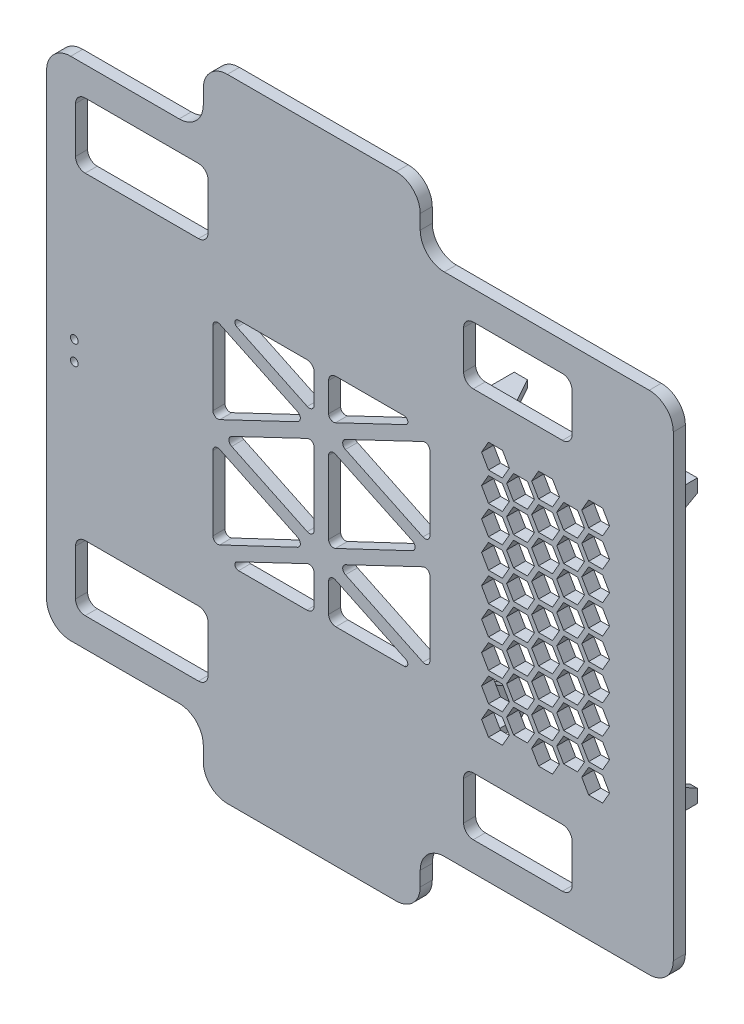
SolidWorks part; units mm, degrees
ref_plane "前视基准面" through (0, 0, 0) normal (0, 0, 1) x (1, 0, 0)
ref_plane "上视基准面" through (0, 0, 0) normal (0, 1, 0) x (1, 0, 0)
ref_plane "右视基准面" through (0, 0, 0) normal (1, 0, 0) x (0, 0, -1)
sketch "草图1" plane through (0, 0, 0) normal (0, 0, 1) x (1, 0, 0)
  line L2 (-130, 95) -> (-130, -95)
  line L3 (-120, -105) -> (-75, -105)
  line L4 (130, 95) -> (130, -95)
  line L5 (126.7518, 102.3765) -> (130, 105) construction
  line L6 (-130, -105) -> (-126.7518, -102.3765) construction
  line L9 (-65, -115) -> (-65, -121)
  line L10 (-55, -131) -> (15, -131)
  line L11 (25, -121) -> (25, -115)
  line L13 (35, -105) -> (120, -105)
  line L14 (126.7518, -102.3765) -> (130, -105) construction
  line L15 (-130, 105) -> (-126.7518, 102.3765) construction
  line L16 (-130, 0) -> (130, 0) construction
  line L17 (35, 105) -> (120, 105)
  line L18 (25, 121) -> (25, 115)
  line L19 (-55, 131) -> (15, 131)
  line L20 (-65, 115) -> (-65, 121)
  line L21 (-120, 105) -> (-75, 105)
  arc A1 (-120, -105) -> (-130, -95) centre (-120, -95) cw
  arc A3 (120, -105) -> (130, -95) centre (120, -95) ccw
  arc A8 (-65, -115) -> (-75, -105) centre (-75, -115) ccw
  arc A9 (25, -115) -> (35, -105) centre (35, -115) cw
  arc A10 (-55, -131) -> (-65, -121) centre (-55, -121) cw
  arc A11 (15, -131) -> (25, -121) centre (15, -121) ccw
  arc A12 (15, 131) -> (25, 121) centre (15, 121) cw
  arc A13 (-55, 131) -> (-65, 121) centre (-55, 121) ccw
  arc A14 (25, 115) -> (35, 105) centre (35, 115) ccw
  arc A15 (-65, 115) -> (-75, 105) centre (-75, 115) cw
  arc A16 (120, 105) -> (130, 95) centre (120, 95) cw
  arc A17 (-120, 105) -> (-130, 95) centre (-120, 95) ccw
  point P0 (0, 0)
  point P40 (25, -105)
  point P45 (25, 105)
  dimension "D2" = 10
  dimension "D3" = 65
  dimension "D4" = 10
  dimension "D5" = 105
  dimension "D7" = 10
  dimension "D8" = 10
  dimension "D10" = 10
  dimension "D12" = 10
  dimension "D13" = 105
  dimension "D18" = 90
  dimension "D19" = 6
extrude "凸台-拉伸1" add sketch "草图1" along normal blind 5
sketch "草图4" plane through (0, 0, 0) normal (0, 0, -1) x (-1, 0, 0)
  line L0 (-39, -47.5) -> (-39, -58.5)
  line L1 (-39, -58.5) -> (-50, -58.5)
  line L2 (-50, -58.5) -> (-50, -55.5)
  line L3 (-50, -55.5) -> (-42, -55.5)
  line L4 (-42, -55.5) -> (-42, -47.5)
  line L5 (-42, -47.5) -> (-39, -47.5)
  line L6 (-130, 0) -> (-25.5592, 0) construction
  line L7 (-130, -95) -> (-130, 95) construction
  line L10 (-130, -95) -> (-130, 95) construction
  dimension "D1" = 11
  dimension "D2" = 11
  dimension "D3" = 3
  dimension "D4" = 3
  dimension "D5" = 80
  dimension "D7" = 55.5
extrude "凸台-拉伸2" add sketch "草图4" along normal blind 20
sketch "草图5" plane through (0, -58.5, 0) normal (0, -1, 0) x (1, 0, 0)
  line L0 (50, -10) -> (44.5, -20)
  line L1 (50, -20) -> (50, 0) construction
  line L2 (50, -20) -> (39, -20) construction
  line L3 (44.5, -20) -> (50, -20)
  line L4 (50, -20) -> (50, -10)
  dimension "D1" = 10
  dimension "D2" = 5.5
extrude "切除-拉伸3" cut sketch "草图5" against normal blind 10
sketch "草图6" plane through (39, 0, 0) normal (-1, 0, 0) x (0, 0, 1)
  line L0 (-20, -53) -> (-10, -47.5)
  line L1 (-20, -58.5) -> (-20, -47.5) construction
  line L2 (-20, -47.5) -> (0, -47.5) construction
  line L3 (-10, -47.5) -> (-20, -47.5)
  line L4 (-20, -47.5) -> (-20, -53)
  dimension "D1" = 10
  dimension "D2" = 5.5
extrude "切除-拉伸4" cut sketch "草图6" against normal blind 10
ref_plane "基准面2" through (77, 0, 0) normal (1, 0, 0) x (0, 0, -1)
mirror "镜向1" about plane through (77, 0, 0) normal (1, 0, 0) of "凸台-拉伸2", "切除-拉伸4", "切除-拉伸3"
mirror "镜向2" about plane through (0, 0, 0) normal (0, 1, 0) of "镜向1"
sketch "草图7" plane through (0, 0, 0) normal (0, 0, -1) x (-1, 0, 0)
  line L4 (-112, -55.5) -> (-104, -55.5) construction
  line L5 (-112, 47.5) -> (-112, 55.5) construction
  line L6 (-112, 55.5) -> (-104, 55.5) construction
  line L7 (-92.013, 36) -> (-94.8997, 41)
  line L8 (-94.8997, 41) -> (-100.6732, 41)
  line L9 (-100.6732, 41) -> (-103.56, 36)
  line L10 (-103.56, 36) -> (-100.6732, 31)
  line L11 (-100.6732, 31) -> (-94.8997, 31)
  line L12 (-94.8997, 31) -> (-92.013, 36)
  line L13 (-77.0019, 36) -> (-97.7865, 36) construction
  line L14 (-74.1151, 31) -> (-71.2284, 36)
  line L15 (-71.2284, 36) -> (-74.1151, 41)
  line L16 (-74.1151, 41) -> (-79.8886, 41)
  line L17 (-79.8886, 41) -> (-82.7754, 36)
  line L18 (-82.7754, 36) -> (-79.8886, 31)
  line L19 (-79.8886, 31) -> (-74.1151, 31)
  line L20 (-92.013, 24) -> (-94.8997, 29)
  line L21 (-93.1677, 30) -> (-90.2809, 25)
  line L22 (-90.2809, 25) -> (-84.5074, 25)
  line L23 (-84.5074, 25) -> (-81.6207, 30)
  line L24 (-81.6207, 30) -> (-84.5074, 35)
  line L25 (-84.5074, 35) -> (-90.2809, 35)
  line L26 (-90.2809, 35) -> (-93.1677, 30)
  line L27 (-84.5074, 37) -> (-81.6207, 42)
  line L28 (-81.6207, 42) -> (-84.5074, 47)
  line L29 (-84.5074, 47) -> (-90.2809, 47)
  line L30 (-90.2809, 47) -> (-93.1677, 42)
  line L31 (-93.1677, 42) -> (-90.2809, 37)
  line L32 (-90.2809, 37) -> (-84.5074, 37)
  line L33 (-79.8886, 43) -> (-74.1151, 43)
  line L34 (-74.1151, 43) -> (-71.2284, 48)
  line L35 (-71.2284, 48) -> (-74.1151, 53)
  line L36 (-74.1151, 53) -> (-79.8886, 53)
  line L37 (-79.8886, 53) -> (-82.7754, 48)
  line L38 (-82.7754, 48) -> (-79.8886, 43)
  line L39 (-94.8997, 43) -> (-92.013, 48)
  line L40 (-92.013, 48) -> (-94.8997, 53)
  line L41 (-94.8997, 53) -> (-100.6732, 53)
  line L42 (-100.6732, 53) -> (-103.56, 48)
  line L43 (-103.56, 48) -> (-100.6732, 43)
  line L44 (-100.6732, 43) -> (-94.8997, 43)
  line L45 (-72.3831, 42) -> (-69.4963, 37)
  line L46 (-69.4963, 37) -> (-63.7228, 37)
  line L47 (-63.7228, 37) -> (-60.8361, 42)
  line L48 (-60.8361, 42) -> (-63.7228, 47)
  line L49 (-63.7228, 47) -> (-69.4963, 47)
  line L50 (-69.4963, 47) -> (-72.3831, 42)
  line L51 (-94.8997, 29) -> (-100.6732, 29)
  line L52 (-100.6732, 29) -> (-103.56, 24)
  line L53 (-103.56, 24) -> (-100.6732, 19)
  line L54 (-100.6732, 19) -> (-94.8997, 19)
  line L55 (-94.8997, 19) -> (-92.013, 24)
  line L56 (-93.1677, 18) -> (-90.2809, 13)
  line L57 (-90.2809, 13) -> (-84.5074, 13)
  line L58 (-84.5074, 13) -> (-81.6207, 18)
  line L59 (-81.6207, 18) -> (-84.5074, 23)
  line L60 (-84.5074, 23) -> (-90.2809, 23)
  line L61 (-90.2809, 23) -> (-93.1677, 18)
  line L62 (-74.1151, 19) -> (-71.2284, 24)
  line L63 (-71.2284, 24) -> (-74.1151, 29)
  line L64 (-74.1151, 29) -> (-79.8886, 29)
  line L65 (-79.8886, 29) -> (-82.7754, 24)
  line L66 (-82.7754, 24) -> (-79.8886, 19)
  line L67 (-79.8886, 19) -> (-74.1151, 19)
  line L68 (-72.3831, 30) -> (-69.4963, 25)
  line L69 (-69.4963, 25) -> (-63.7228, 25)
  line L70 (-63.7228, 25) -> (-60.8361, 30)
  line L71 (-60.8361, 30) -> (-63.7228, 35)
  line L72 (-63.7228, 35) -> (-69.4963, 35)
  line L73 (-69.4963, 35) -> (-72.3831, 30)
  line L74 (-92.013, 12) -> (-94.8997, 17)
  line L75 (-94.8997, 17) -> (-100.6732, 17)
  line L76 (-100.6732, 17) -> (-103.56, 12)
  line L77 (-103.56, 12) -> (-100.6732, 7)
  line L78 (-100.6732, 7) -> (-94.8997, 7)
  line L79 (-94.8997, 7) -> (-92.013, 12)
  line L80 (-93.1677, 6) -> (-90.2809, 1)
  line L81 (-90.2809, 1) -> (-84.5074, 1)
  line L82 (-84.5074, 1) -> (-81.6207, 6)
  line L83 (-81.6207, 6) -> (-84.5074, 11)
  line L84 (-84.5074, 11) -> (-90.2809, 11)
  line L85 (-90.2809, 11) -> (-93.1677, 6)
  line L86 (-74.1151, 7) -> (-71.2284, 12)
  line L87 (-71.2284, 12) -> (-74.1151, 17)
  line L88 (-74.1151, 17) -> (-79.8886, 17)
  line L89 (-79.8886, 17) -> (-82.7754, 12)
  line L90 (-82.7754, 12) -> (-79.8886, 7)
  line L91 (-79.8886, 7) -> (-74.1151, 7)
  line L92 (-72.3831, 18) -> (-69.4963, 13)
  line L93 (-69.4963, 13) -> (-63.7228, 13)
  line L94 (-63.7228, 13) -> (-60.8361, 18)
  line L95 (-60.8361, 18) -> (-63.7228, 23)
  line L96 (-63.7228, 23) -> (-69.4963, 23)
  line L97 (-69.4963, 23) -> (-72.3831, 18)
  line L98 (-92.013, 0) -> (-94.8997, 5)
  line L99 (-94.8997, 5) -> (-100.6732, 5)
  line L100 (-100.6732, 5) -> (-103.56, 0)
  line L101 (-103.56, 0) -> (-100.6732, -5)
  line L102 (-100.6732, -5) -> (-94.8997, -5)
  line L103 (-94.8997, -5) -> (-92.013, 0)
  line L104 (-93.1677, -6) -> (-90.2809, -11)
  line L105 (-90.2809, -11) -> (-84.5074, -11)
  line L106 (-84.5074, -11) -> (-81.6207, -6)
  line L107 (-81.6207, -6) -> (-84.5074, -1)
  line L108 (-84.5074, -1) -> (-90.2809, -1)
  line L109 (-90.2809, -1) -> (-93.1677, -6)
  line L110 (-74.1151, -5) -> (-71.2284, 0)
  line L111 (-71.2284, 0) -> (-74.1151, 5)
  line L112 (-74.1151, 5) -> (-79.8886, 5)
  line L113 (-79.8886, 5) -> (-82.7754, 0)
  line L114 (-82.7754, 0) -> (-79.8886, -5)
  line L115 (-79.8886, -5) -> (-74.1151, -5)
  line L116 (-72.3831, 6) -> (-69.4963, 1)
  line L117 (-69.4963, 1) -> (-63.7228, 1)
  line L118 (-63.7228, 1) -> (-60.8361, 6)
  line L119 (-60.8361, 6) -> (-63.7228, 11)
  line L120 (-63.7228, 11) -> (-69.4963, 11)
  line L121 (-69.4963, 11) -> (-72.3831, 6)
  line L122 (-92.013, -12) -> (-94.8997, -7)
  line L123 (-94.8997, -7) -> (-100.6732, -7)
  line L124 (-100.6732, -7) -> (-103.56, -12)
  line L125 (-103.56, -12) -> (-100.6732, -17)
  line L126 (-100.6732, -17) -> (-94.8997, -17)
  line L127 (-94.8997, -17) -> (-92.013, -12)
  line L128 (-93.1677, -18) -> (-90.2809, -23)
  line L129 (-90.2809, -23) -> (-84.5074, -23)
  line L130 (-84.5074, -23) -> (-81.6207, -18)
  line L131 (-81.6207, -18) -> (-84.5074, -13)
  line L132 (-84.5074, -13) -> (-90.2809, -13)
  line L133 (-90.2809, -13) -> (-93.1677, -18)
  line L134 (-74.1151, -17) -> (-71.2284, -12)
  line L135 (-71.2284, -12) -> (-74.1151, -7)
  line L136 (-74.1151, -7) -> (-79.8886, -7)
  line L137 (-79.8886, -7) -> (-82.7754, -12)
  line L138 (-82.7754, -12) -> (-79.8886, -17)
  line L139 (-79.8886, -17) -> (-74.1151, -17)
  line L140 (-72.3831, -6) -> (-69.4963, -11)
  line L141 (-69.4963, -11) -> (-63.7228, -11)
  line L142 (-63.7228, -11) -> (-60.8361, -6)
  line L143 (-60.8361, -6) -> (-63.7228, -1)
  line L144 (-63.7228, -1) -> (-69.4963, -1)
  line L145 (-69.4963, -1) -> (-72.3831, -6)
  line L146 (-92.013, -24) -> (-94.8997, -19)
  line L147 (-94.8997, -19) -> (-100.6732, -19)
  line L148 (-100.6732, -19) -> (-103.56, -24)
  line L149 (-103.56, -24) -> (-100.6732, -29)
  line L150 (-100.6732, -29) -> (-94.8997, -29)
  line L151 (-94.8997, -29) -> (-92.013, -24)
  line L152 (-93.1677, -30) -> (-90.2809, -35)
  line L153 (-90.2809, -35) -> (-84.5074, -35)
  line L154 (-84.5074, -35) -> (-81.6207, -30)
  line L155 (-81.6207, -30) -> (-84.5074, -25)
  line L156 (-84.5074, -25) -> (-90.2809, -25)
  line L157 (-90.2809, -25) -> (-93.1677, -30)
  line L158 (-74.1151, -29) -> (-71.2284, -24)
  line L159 (-71.2284, -24) -> (-74.1151, -19)
  line L160 (-74.1151, -19) -> (-79.8886, -19)
  line L161 (-79.8886, -19) -> (-82.7754, -24)
  line L162 (-82.7754, -24) -> (-79.8886, -29)
  line L163 (-79.8886, -29) -> (-74.1151, -29)
  line L164 (-72.3831, -18) -> (-69.4963, -23)
  line L165 (-69.4963, -23) -> (-63.7228, -23)
  line L166 (-63.7228, -23) -> (-60.8361, -18)
  line L167 (-60.8361, -18) -> (-63.7228, -13)
  line L168 (-63.7228, -13) -> (-69.4963, -13)
  line L169 (-69.4963, -13) -> (-72.3831, -18)
  line L170 (-92.013, -36) -> (-94.8997, -31)
  line L171 (-94.8997, -31) -> (-100.6732, -31)
  line L172 (-100.6732, -31) -> (-103.56, -36)
  line L173 (-103.56, -36) -> (-100.6732, -41)
  line L174 (-100.6732, -41) -> (-94.8997, -41)
  line L175 (-94.8997, -41) -> (-92.013, -36)
  line L176 (-93.1677, -42) -> (-90.2809, -47)
  line L177 (-90.2809, -47) -> (-84.5074, -47)
  line L178 (-84.5074, -47) -> (-81.6207, -42)
  line L179 (-81.6207, -42) -> (-84.5074, -37)
  line L180 (-84.5074, -37) -> (-90.2809, -37)
  line L181 (-90.2809, -37) -> (-93.1677, -42)
  line L182 (-74.1151, -41) -> (-71.2284, -36)
  line L183 (-71.2284, -36) -> (-74.1151, -31)
  line L184 (-74.1151, -31) -> (-79.8886, -31)
  line L185 (-79.8886, -31) -> (-82.7754, -36)
  line L186 (-82.7754, -36) -> (-79.8886, -41)
  line L187 (-79.8886, -41) -> (-74.1151, -41)
  line L188 (-72.3831, -30) -> (-69.4963, -35)
  line L189 (-69.4963, -35) -> (-63.7228, -35)
  line L190 (-63.7228, -35) -> (-60.8361, -30)
  line L191 (-60.8361, -30) -> (-63.7228, -25)
  line L192 (-63.7228, -25) -> (-69.4963, -25)
  line L193 (-69.4963, -25) -> (-72.3831, -30)
  line L194 (-92.013, -48) -> (-94.8997, -43)
  line L195 (-94.8997, -43) -> (-100.6732, -43)
  line L196 (-100.6732, -43) -> (-103.56, -48)
  line L197 (-103.56, -48) -> (-100.6732, -53)
  line L198 (-100.6732, -53) -> (-94.8997, -53)
  line L199 (-94.8997, -53) -> (-92.013, -48)
  line L206 (-74.1151, -53) -> (-71.2284, -48)
  line L207 (-71.2284, -48) -> (-74.1151, -43)
  line L208 (-74.1151, -43) -> (-79.8886, -43)
  line L209 (-79.8886, -43) -> (-82.7754, -48)
  line L210 (-82.7754, -48) -> (-79.8886, -53)
  line L211 (-79.8886, -53) -> (-74.1151, -53)
  line L212 (-72.3831, -42) -> (-69.4963, -47)
  line L213 (-69.4963, -47) -> (-63.7228, -47)
  line L214 (-63.7228, -47) -> (-60.8361, -42)
  line L215 (-60.8361, -42) -> (-63.7228, -37)
  line L216 (-63.7228, -37) -> (-69.4963, -37)
  line L217 (-69.4963, -37) -> (-72.3831, -42)
  line L218 (-61.9908, 36) -> (-59.104, 31)
  line L219 (-61.9908, 48) -> (-59.104, 43)
  line L220 (-59.104, 43) -> (-53.3305, 43)
  line L221 (-53.3305, 43) -> (-50.4438, 48)
  line L222 (-50.4438, 48) -> (-53.3305, 53)
  line L223 (-53.3305, 53) -> (-59.104, 53)
  line L224 (-59.104, 53) -> (-61.9908, 48)
  line L225 (-59.104, 31) -> (-53.3305, 31)
  line L226 (-53.3305, 31) -> (-50.4438, 36)
  line L227 (-50.4438, 36) -> (-53.3305, 41)
  line L228 (-53.3305, 41) -> (-59.104, 41)
  line L229 (-59.104, 41) -> (-61.9908, 36)
  line L230 (-61.9908, 24) -> (-59.104, 19)
  line L231 (-59.104, 19) -> (-53.3305, 19)
  line L232 (-53.3305, 19) -> (-50.4438, 24)
  line L233 (-50.4438, 24) -> (-53.3305, 29)
  line L234 (-53.3305, 29) -> (-59.104, 29)
  line L235 (-59.104, 29) -> (-61.9908, 24)
  line L236 (-61.9908, 12) -> (-59.104, 7)
  line L237 (-59.104, 7) -> (-53.3305, 7)
  line L238 (-53.3305, 7) -> (-50.4438, 12)
  line L239 (-50.4438, 12) -> (-53.3305, 17)
  line L240 (-53.3305, 17) -> (-59.104, 17)
  line L241 (-59.104, 17) -> (-61.9908, 12)
  line L242 (-61.9908, 0) -> (-59.104, -5)
  line L243 (-59.104, -5) -> (-53.3305, -5)
  line L244 (-53.3305, -5) -> (-50.4438, 0)
  line L245 (-50.4438, 0) -> (-53.3305, 5)
  line L246 (-53.3305, 5) -> (-59.104, 5)
  line L247 (-59.104, 5) -> (-61.9908, 0)
  line L248 (-61.9908, -12) -> (-59.104, -17)
  line L249 (-59.104, -17) -> (-53.3305, -17)
  line L250 (-53.3305, -17) -> (-50.4438, -12)
  line L251 (-50.4438, -12) -> (-53.3305, -7)
  line L252 (-53.3305, -7) -> (-59.104, -7)
  line L253 (-59.104, -7) -> (-61.9908, -12)
  line L254 (-61.9908, -24) -> (-59.104, -29)
  line L255 (-59.104, -29) -> (-53.3305, -29)
  line L256 (-53.3305, -29) -> (-50.4438, -24)
  line L257 (-50.4438, -24) -> (-53.3305, -19)
  line L258 (-53.3305, -19) -> (-59.104, -19)
  line L259 (-59.104, -19) -> (-61.9908, -24)
  line L260 (-61.9908, -36) -> (-59.104, -41)
  line L261 (-59.104, -41) -> (-53.3305, -41)
  line L262 (-53.3305, -41) -> (-50.4438, -36)
  line L263 (-50.4438, -36) -> (-53.3305, -31)
  line L264 (-53.3305, -31) -> (-59.104, -31)
  line L265 (-59.104, -31) -> (-61.9908, -36)
  line L266 (-61.9908, -48) -> (-59.104, -53)
  line L267 (-59.104, -53) -> (-53.3305, -53)
  line L268 (-53.3305, -53) -> (-50.4438, -48)
  line L269 (-50.4438, -48) -> (-53.3305, -43)
  line L270 (-53.3305, -43) -> (-59.104, -43)
  line L271 (-59.104, -43) -> (-61.9908, -48)
  line L272 (-93.1677, -54) -> (-90.2809, -59) [skipped]
  line L273 (-90.2809, -59) -> (-84.5074, -59) [skipped]
  line L274 (-84.5074, -59) -> (-81.6207, -54) [skipped]
  line L275 (-81.6207, -54) -> (-84.5074, -49) [skipped]
  line L276 (-84.5074, -49) -> (-90.2809, -49) [skipped]
  line L277 (-90.2809, -49) -> (-93.1677, -54) [skipped]
  circle A0 centre (-97.7865, 36) radius 5 construction
  circle A1 centre (-77.0019, 36) radius 5 construction
  circle A2 centre (-87.3942, 30) radius 5 construction
  circle A3 centre (-87.3942, 42) radius 5 construction
  circle A4 centre (-77.0019, 48) radius 5 construction
  circle A5 centre (-97.7865, 48) radius 5 construction
  circle A6 centre (-66.6096, 42) radius 5 construction
  circle A7 centre (-56.2173, 48) radius 5 construction
  point P4 (-87.3942, 37)
  dimension "D1" = 2
  dimension "D3" = 10
  dimension "D4" = 10
  dimension "D5" = 2
  dimension "D7" = 10
  dimension "D11" = 10
  dimension "D14" = 10
  dimension "D15" = 10
  dimension "D20" = 10
  dimension "D2" = 2
  dimension "D6" = 2
  dimension "D8" = 2
  dimension "D9" = 2
  dimension "D10" = 2
  dimension "D12" = 2
  dimension "D13" = 2
  dimension "D16" = 2
  dimension "D17" = 2
  dimension "D19" = 2
  dimension "D21" = 9
  dimension "D22" = 2.5
  dimension "D23" = 2.5
  dimension "D24" = 8.44
  dimension "D18" = 8
extrude "切除-拉伸5" cut sketch "草图7" against normal blind 5
sketch "草图8" plane through (0, 0, 0) normal (0, 0, -1) x (-1, 0, 0)
  line L0 (-75.3677, 120) -> (-75.3677, -120)
  line L1 (-100.0285, 77.2863) -> (-100.0285, -77.2863)
  line L2 (-100.0285, 77.2863) -> (-75.3677, 120)
  line L3 (-100.0285, -77.2863) -> (-75.3677, -120)
  line L4 (-37.1297, 0) -> (-146.8562, 0) construction
  dimension "D1" = 30
  dimension "D2" = 30
  dimension "D3" = 120
  dimension "D4" = 120
sketch "草图9" plane through (0, 0, 0) normal (0, 0, -1) x (-1, 0, 0)
  line L0 (148.8518, 0) -> (-37.1297, 0) construction
  line L1 (-29, 41) -> (-29, 4)
  line L2 (-25, -45) -> (13, -45)
  line L3 (61, -41) -> (61, -4)
  line L4 (57, 45) -> (19, 45)
  line L14 (-29, 41) -> (9.8049, 22.5)
  line L15 (57, 0) -> (19, -18.1163)
  line L16 (130, 95) -> (130, -95) construction
  line L17 (63, 93) -> (118, 93)
  line L18 (63, 93) -> (63, 66)
  line L19 (63, 66) -> (118, 66)
  line L20 (118, 93) -> (118, 66)
  line L21 (75, 105) -> (120, 105) construction
  line L22 (63, -66) -> (118, -66)
  line L23 (118, -93) -> (118, -66)
  line L24 (63, -93) -> (118, -93)
  line L25 (63, -93) -> (63, -66)
  line L26 (-120, 105) -> (-35, 105) construction
  line L27 (-43, 93) -> (-88, 93)
  line L28 (-43, 93) -> (-43, 69)
  line L29 (-43, 69) -> (-88, 69)
  line L30 (-88, 93) -> (-88, 69)
  line L31 (-130, -95) -> (-130, 95) construction
  line L32 (-43, -69) -> (-88, -69)
  line L33 (-88, -93) -> (-88, -69)
  line L34 (-43, -93) -> (-88, -93)
  line L35 (-43, -93) -> (-43, -69)
  line L36 (-25, 45) -> (13, 26.8837)
  line L37 (-25, -45) -> (13, -26.8837)
  line L38 (61, 41) -> (22.0746, 22.5575)
  line L39 (-25.5359, 0) -> (13, -18.258)
  line L40 (57, 45) -> (19, 26.8837)
  line L41 (57, -45) -> (19, -26.8837)
  line L42 (16, 61.4977) -> (16, -60.5731) construction
  line L43 (13, 45) -> (13, 26.8837)
  line L44 (19, 45) -> (19, 26.8837)
  line L45 (13, 18.258) -> (13, -18.258)
  line L46 (9.8049, 22.5) -> (-29, 4)
  line L47 (19, 18.1163) -> (57, 0)
  line L48 (22.0746, 22.5575) -> (61, 4)
  line L49 (13, 18.258) -> (-25.5359, 0)
  line L50 (19, 18.1163) -> (19, -18.1163)
  line L51 (22.0746, -22.5575) -> (61, -41)
  line L52 (9.8049, -22.5) -> (-29, -41)
  line L53 (9.8049, -22.5) -> (-29, -4)
  line L54 (22.0746, -22.5575) -> (61, -4)
  line L55 (13, -26.8837) -> (13, -45)
  line L56 (19, -26.8837) -> (19, -45)
  line L57 (13, 45) -> (-25, 45)
  line L58 (-29, -4) -> (-29, -41)
  line L59 (19, -45) -> (57, -45)
  line L60 (61, 4) -> (61, 41)
  line L61 (-44, 41) -> (-44, -37.8122) construction
  dimension "D1" = 45
  dimension "D2" = 45
  dimension "D3" = 15
  dimension "D4" = 90
  dimension "D5" = 1
  dimension "D7" = 12
  dimension "D8" = 12
  dimension "D9" = 27
  dimension "D10" = 55
  dimension "D11" = 12
  dimension "D12" = 45
  dimension "D13" = 42
  dimension "D14" = 24
  dimension "D21" = 4
  dimension "D22" = 4
  dimension "D23" = 4
  dimension "D24" = 4
  dimension "D26" = 4
  dimension "D27" = 3
  dimension "D28" = 45
extrude "切除-拉伸6" cut sketch "草图9" against normal blind 5 contours L27 L30 L29 L28 | L34 L35 L32 L33 | L25 L24 L23 L22 | L20 L17 L18 L19 | L4 L44 L40 | L48 L60 L38 | L47 L50 L15 | L54 L51 L3 | L56 L59 L41 | L55 L37 L2 | L53 L58 L52 | L45 L49 L39 | L46 L14 L1 | L43 L57 L36 | L57 L36 L43 region at (16.065, 22.5, 0) region at (-0.3333, -38.9612, 0) region at (-48.0249, -22.5192, 0) region at (-31.6667, 38.9612, 0) region at (-31.6667, 0, 0) region at (-90.5, 79.5, 0) region at (-90.5, -79.5, 0) region at (65.5, 81, 0) region at (65.5, -81, 0) region at (-0.3333, 38.9612, 0) region at (-48.0249, 22.5192, 0) region at (-0.1547, 0, 0) region at (-31.6667, -38.9612, 0) region at (16.065, -22.5, 0)
fillet "圆角1" radius 4 16 edges at (-63, -93, 2.5) (-63, -66, 2.5) (-118, -93, 2.5) (-118, -66, 2.5) (-63, 66, 2.5) (-118, 66, 2.5) (-118, 93, 2.5) (-63, 93, 2.5) (43, -93, 2.5) (88, -69, 2.5) (43, -69, 2.5) (88, -93, 2.5) (88, 69, 2.5) (43, 69, 2.5) (43, 93, 2.5) (88, 93, 2.5)
fillet "圆角2" radius 1.5 4 edges at (25, -45, 2.5) (-57, -45, 2.5) (25, 45, 2.5) (-57, 45, 2.5)
fillet "圆角3" radius 2 22 edges at (29, -4, 2.5) (29, 4, 2.5) (-13, -18.258, 2.5) (-61, -41, 2.5) (-61, 4, 2.5) (-13, -26.8837, 2.5) (-13, 18.258, 2.5) (-61, -4, 2.5) (-22.0746, -22.5575, 2.5) (25.5359, 0, 2.5) (-22.0746, 22.5575, 2.5) (-61, 41, 2.5) (-19, 26.8837, 2.5) (-19, -26.8837, 2.5) (-19, -18.1163, 2.5) (29, -41, 2.5) (29, 41, 2.5) (-57, 0, 2.5) (-9.8049, -22.5, 2.5) (-13, 26.8837, 2.5) (-9.8049, 22.5, 2.5) (-19, 18.1163, 2.5)
fillet "圆角4" radius 3 4 edges at (-13, -45, 2.5) (-13, 45, 2.5) (-19, -45, 2.5) (-19, 45, 2.5)
sketch "草图10" plane through (0, 0, 5) normal (0, 0, 1) x (1, 0, 0)
  line L0 (-121, -6.5) -> (-116, -1.6)
  line L1 (-116, 1.6) -> (-121, 6.5)
  circle A0 centre (-118.5, -4.05) radius 1.6
  circle A1 centre (-118.5, 4.05) radius 1.6
extrude "切除-拉伸7" cut sketch "草图10" along normal blind 3 and the other way blind 8 contours L0 A0 | L0 A0 | L1 A1 | L1 A1 region at (-118.9753, -3.565, 5) region at (-118.0247, -4.535, 5) region at (-118.9753, 3.565, 5) region at (-118.0247, 4.535, 5)
equation "\"45、\"=43.7672"
